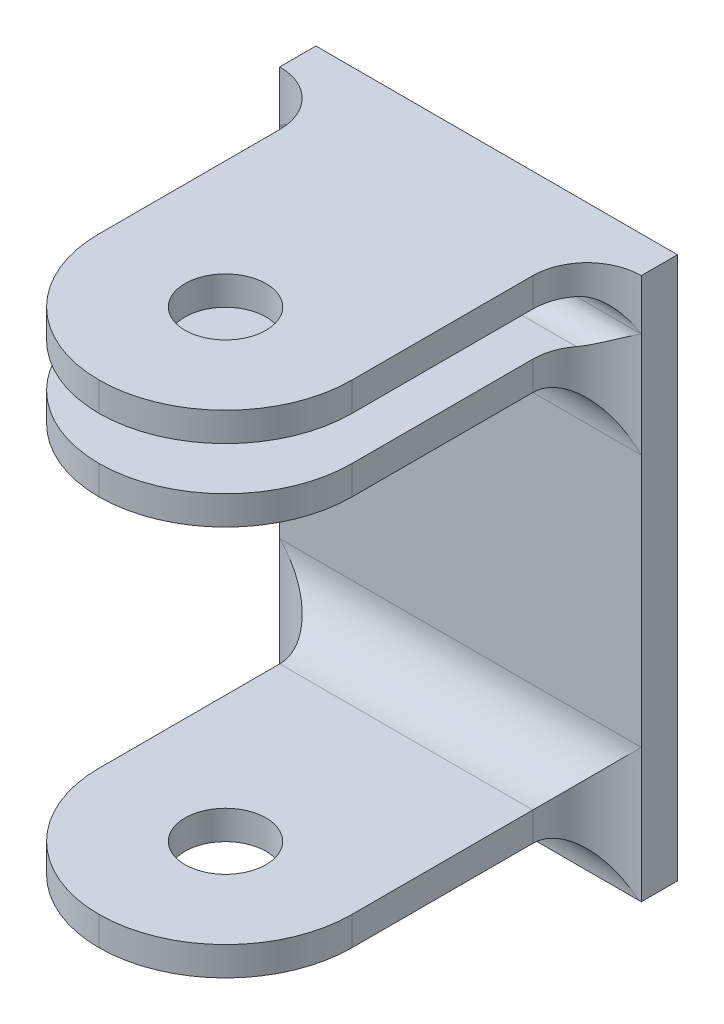
SolidWorks part; units mm, degrees
ref_plane "Plan de face" through (0, 0, 0) normal (1, 0, 0) x (0, 1, 0)
ref_plane "Plan de dessus" through (0, 0, 0) normal (0, 0, 1) x (0, 1, 0)
ref_plane "Plan de droite" through (0, 0, 0) normal (0, 1, 0) x (-1, 0, 0)
sketch "Esquisse1" plane through (0, 0, 0) normal (0, 0, 1) x (0, 1, 0)
  line L1 (0, 0) -> (150, 0)
  line L2 (0, 0) -> (0, 100)
  line L3 (0, 100) -> (150, 100)
  line L4 (150, 0) -> (150, 100)
  dimension "D1" = 150
  dimension "D2" = 100
extrude "Boss.-Extru.1" add sketch "Esquisse1" along normal blind 10
sketch "Esquisse2" plane through (0, 0, 10) normal (0, 0, 1) x (1, 0, 0)
  line L0 (-100, 150) -> (-100, 0) construction
  line L1 (-85, 130) -> (-15, 130)
  line L2 (-85, 130) -> (-85, 122)
  line L3 (-85, 122) -> (-15, 122)
  line L4 (-15, 130) -> (-15, 122)
  line L5 (-85, 150) -> (-15, 150)
  line L6 (0, 0) -> (0, 150) construction
  line L7 (0, 150) -> (-100, 150) construction
  line L8 (-85, 22) -> (-15, 22)
  line L9 (-85, 22) -> (-85, 14)
  line L10 (-85, 14) -> (-15, 14)
  line L11 (-15, 22) -> (-15, 14)
  line L12 (-85, 150) -> (-85, 142)
  line L13 (-85, 142) -> (-15, 142)
  line L14 (-15, 150) -> (-15, 142)
  dimension "D1" = 8
  dimension "D2" = 8
  dimension "D3" = 100
  dimension "D4" = 70
  dimension "D5" = 15
  dimension "D6" = 70
  dimension "D7" = 15
  dimension "D8" = 12
  dimension "D9" = 70
  dimension "D10" = 8
  dimension "D11" = 15
extrude "Boss.-Extru.2" add sketch "Esquisse2" along normal blind 100
fillet "Congé1" radius 35 6 edges at (-85, 126, 110) (-15, 126, 110) (-15, 18, 110) (-85, 18, 110) (-85, 146, 110) (-15, 146, 110)
sketch "Esquisse3" plane through (0, 150, 0) normal (0, 1, 0) x (-1, 0, 0)
  line L0 (0, 10) -> (0, 0) construction
  line L2 (0, 0) -> (100, 0) construction
  circle A0 centre (50, 75) radius 11.2
  dimension "D3" = 22.4
  dimension "D1" = 50
  dimension "D2" = 75
extrude "Enlèv. mat.-Extru.1" cut sketch "Esquisse3" against normal blind 150
fillet "Congé2" radius 15 9 edges at (-15, 18, 10) (-50, 22, 10) (-85, 18, 10) (-50, 14, 10) (-85, 146, 10) (-15, 146, 10) (-15, 126, 10) (-50, 122, 10) (-85, 126, 10)
fillet "Congé3" radius 6 2 edges at (-50, 142, 10) (-50, 130, 10)
sketch "Esquisse4" plane through (0, 0, 0) normal (0, -1, 0) x (1, 0, 0)
  line L0 (-100, 10) -> (0, 10) construction
  line L1 (-85.0784, 7.5) -> (-65.0784, 7.5)
  line L2 (-85.0784, 7.5) -> (-85.0784, 2.5)
  line L3 (-85.0784, 2.5) -> (-65.0784, 2.5)
  line L4 (-65.0784, 7.5) -> (-65.0784, 2.5)
  line L5 (-30.993, 7.5) -> (-10.993, 7.5)
  line L6 (-30.993, 7.5) -> (-30.993, 2.5)
  line L7 (-30.993, 2.5) -> (-10.993, 2.5)
  line L8 (-10.993, 7.5) -> (-10.993, 2.5)
  dimension "D1" = 20
  dimension "D2" = 5
  dimension "D3" = 2.5
  dimension "D4" = 5
  dimension "D5" = 20
  dimension "D6" = 2.5
extrude "Enlèv. mat.-Extru.2" cut sketch "Esquisse4" against normal blind 10
